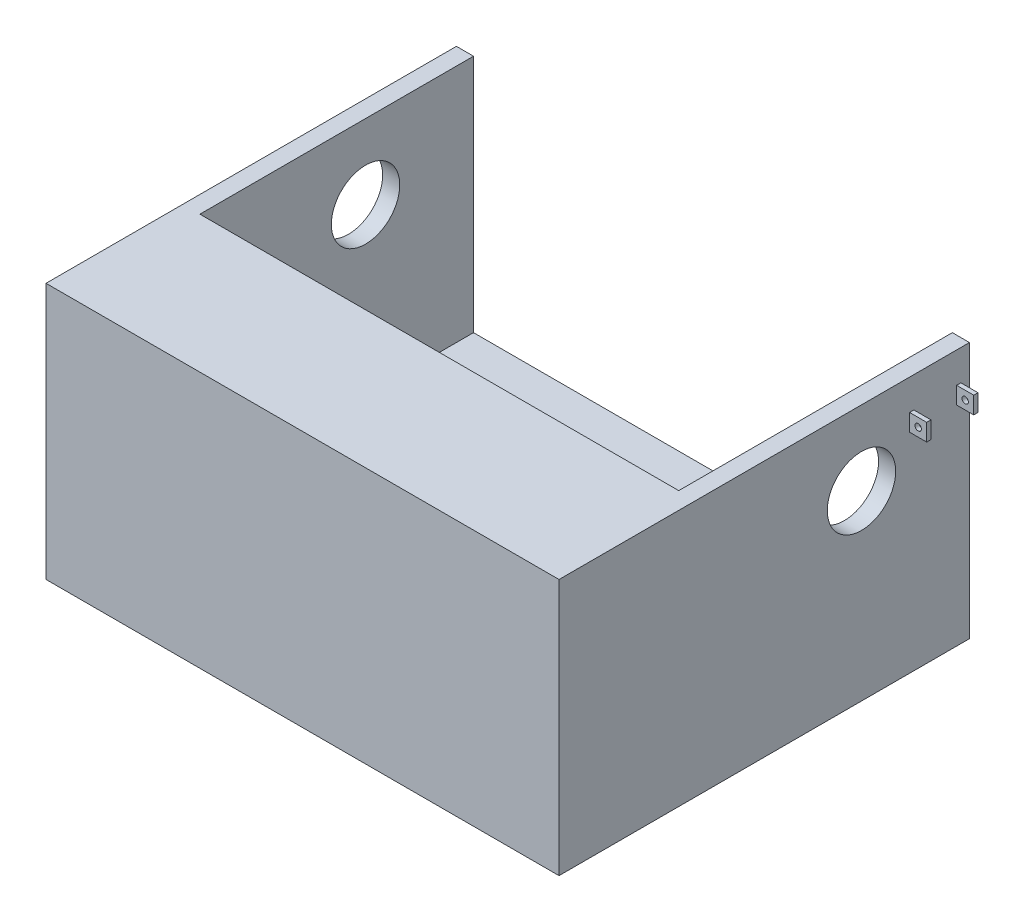
SolidWorks part; units mm, degrees
ref_plane "Front Plane" through (0, 0, 0) normal (0, 0, 1) x (1, 0, 0)
ref_plane "Top Plane" through (0, 0, 0) normal (0, 1, 0) x (1, 0, 0)
ref_plane "Right Plane" through (0, 0, 0) normal (1, 0, 0) x (0, 0, -1)
sketch "Sketch1" plane through (0, 0, 0) normal (0, 0, 1) x (1, 0, 0)
  line L0 (0, 0) -> (762, 0)
  line L1 (55, 0) -> (-55, 0) construction
  line L2 (762, 0) -> (762, 381)
  line L4 (762, 381) -> (0, 381)
  line L5 (762, 381) -> (762, 0)
  line L6 (762, 0) -> (0, 0)
  line L7 (0, 381) -> (0, 0)
  dimension "D1" = 762
  dimension "D2" = 381
extrude "Boss-Extrude1" add sketch "Sketch1" against normal blind 609.6 contours L4 L7 L0 L2 region at (381, 190.5, 0)
sketch "Sketch2" plane through (762, 0, 0) normal (1, 0, 0) x (0, 0, -1)
  line L6 (609.6, 381) -> (0, 381) construction
  line L8 (609.6, 0) -> (609.6, 381) construction
  circle A0 centre (449.228, 270.2231) radius 50.8
  point P10 (609.6, 273.4336)
  dimension "D5" = 101.6
  dimension "D1" = 110.7769
  dimension "D2" = 160.372
sketch "Sketch3" plane through (0, 0, -609.6) normal (0, 0, -1) x (-1, 0, 0)
  line L0 (335.28, 0) -> (-335.28, 0) construction
  line L1 (-736.6, 355.6) -> (-25.4, 355.6)
  line L2 (-736.6, 355.6) -> (-736.6, 25.4)
  line L3 (-736.6, 25.4) -> (-25.4, 25.4)
  line L4 (-25.4, 355.6) -> (-25.4, 25.4)
  line L5 (-762, 381) -> (0, 381) construction
  line L6 (-762, 0) -> (-762, 381) construction
  line L7 (0, 381) -> (0, 0) construction
  dimension "D1" = 25.4
  dimension "D2" = 25.4
  dimension "D3" = 25.4
  dimension "D4" = 25.4
extrude "Cut-Extrude2" cut sketch "Sketch3" against normal blind 584.2
ref_plane "Plane2" through (0, 0, -558.8) normal (0, 0, 1) x (1, 0, 0)
sketch "Sketch5" plane through (0, 0, -558.8) normal (0, 0, 1) x (1, 0, 0)
  line L0 (762, 0) -> (762, 381) construction
  line L1 (762, 335.4937) -> (787.4, 335.4937)
  line L2 (762, 335.4937) -> (762, 310.0937)
  line L3 (762, 310.0937) -> (787.4, 310.0937)
  line L4 (787.4, 335.4937) -> (787.4, 310.0937)
  circle A0 centre (774.7, 322.7937) radius 4.7625
  point P6 (774.7, 310.0937)
  dimension "D3" = 9.525
  dimension "D1" = 25.4
  dimension "D2" = 25.4
  dimension "D4" = 12.7
  dimension "D5" = 12.7
extrude "Boss-Extrude2" add sketch "Sketch5" along normal mid plane 76.2
sketch "Sketch7" plane through (787.4, 0, 0) normal (1, 0, 0) x (0, 0, -1)
  line L0 (520.7, 335.4937) -> (596.9, 335.4937) construction
  line L1 (527.05, 335.4937) -> (590.55, 335.4937)
  line L2 (527.05, 335.4937) -> (527.05, 310.0937)
  line L3 (527.05, 310.0937) -> (590.55, 310.0937)
  line L4 (590.55, 335.4937) -> (590.55, 310.0937)
  line L5 (520.7, 310.0937) -> (596.9, 310.0937) construction
  line L6 (520.7, 310.0937) -> (520.7, 335.4937) construction
  line L7 (596.9, 310.0937) -> (596.9, 335.4937) construction
  dimension "D1" = 6.35
  dimension "D2" = 6.35
extrude "Cut-Extrude4" cut sketch "Sketch7" against normal blind 25.4
ref_plane "Plane3" through (381, 0, 0) normal (1, 0, 0) x (0, 0, -1)
mirror "Mirror3" about plane through (381, 0, 0) normal (1, 0, 0) of "Boss-Extrude2"
sketch "Sketch8" plane through (-25.4, 0, 0) normal (-1, 0, 0) x (0, 0, 1)
  line L0 (-520.7, 335.4937) -> (-596.9, 335.4937) construction
  line L1 (-590.55, 335.4937) -> (-527.05, 335.4937)
  line L2 (-590.55, 335.4937) -> (-590.55, 310.0937)
  line L3 (-590.55, 310.0937) -> (-527.05, 310.0937)
  line L4 (-527.05, 335.4937) -> (-527.05, 310.0937)
  line L5 (-520.7, 310.0937) -> (-596.9, 310.0937) construction
  line L6 (-596.9, 310.0937) -> (-596.9, 335.4937) construction
  line L7 (-520.7, 310.0937) -> (-520.7, 335.4937) construction
  dimension "D1" = 6.35
  dimension "D2" = 6.35
extrude "Cut-Extrude5" cut sketch "Sketch8" against normal blind 25.4
sketch "Sketch14" plane through (0, 0, -609.6) normal (0, 0, -1) x (-1, 0, 0)
  line L0 (-762, 381) -> (0, 381) construction
  line L1 (-25.4, 355.6) -> (-736.6, 355.6)
  line L2 (-25.4, 355.6) -> (-25.4, 381)
  line L3 (-25.4, 381) -> (-736.6, 381)
  line L4 (-736.6, 355.6) -> (-736.6, 381)
  line L5 (-736.6, 355.6) -> (-736.6, 25.4) construction
  dimension "D1" = 0
extrude "Cut-Extrude10" cut sketch "Sketch14" against normal blind 406.4
extrude "Cut-Extrude11" cut sketch "Sketch2" against normal through all
